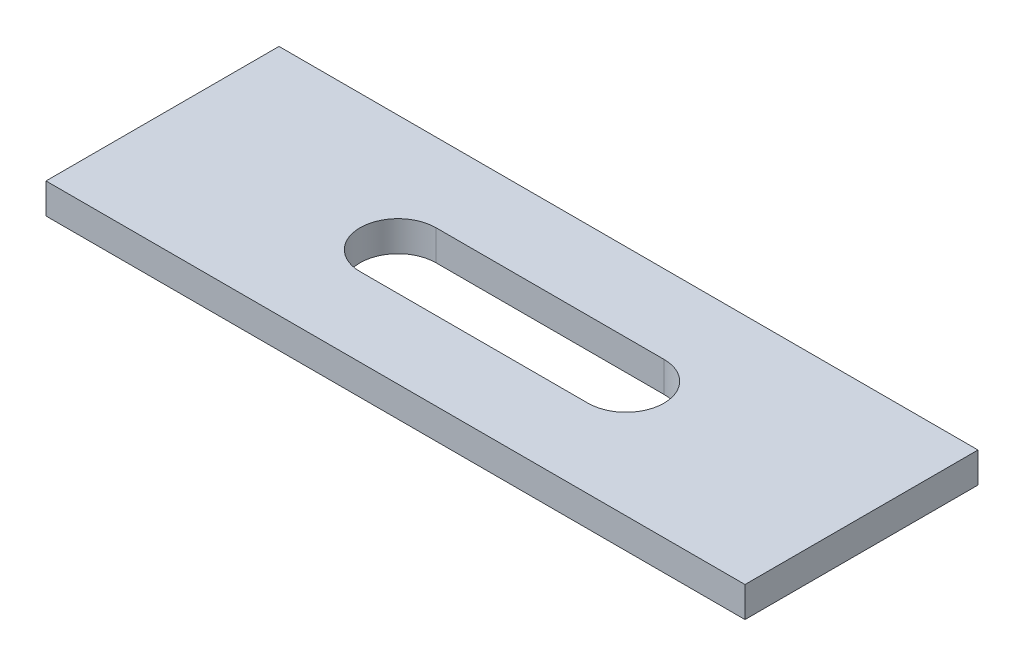
SolidWorks part; units mm, degrees
material "Pine"
ref_plane "Front Plane" through (0, 0, 0) normal (0, 0, 1) x (1, 0, 0)
ref_plane "Top Plane" through (0, 0, 0) normal (0, 1, 0) x (1, 0, 0)
ref_plane "Right Plane" through (0, 0, 0) normal (1, 0, 0) x (0, 0, -1)
sketch "Sketch2" plane through (0, 0, 0) normal (0, 1, 0) x (1, 0, 0)
  line L4 (93, 46) -> (183, 46) construction
  line L5 (0, 0) -> (276, 0)
  line L6 (0, 0) -> (0, 92)
  line L7 (0, 92) -> (276, 92)
  line L8 (276, 0) -> (276, 92)
  line L9 (93, 61) -> (183, 61)
  line L10 (93, 31) -> (183, 31)
  arc A0 (93, 61) -> (93, 31) centre (93, 46) ccw
  arc A1 (183, 31) -> (183, 61) centre (183, 46) ccw
  point P7 (138, 46)
  dimension "D3" = 46
  dimension "D5" = 15
  dimension "D1" = 92
  dimension "D2" = 276
  dimension "D4" = 93
  dimension "D6" = 90
extrude "Boss-Extrude1" add sketch "Sketch2" along normal blind 12 contours L7 L8 L5 L6
extrude "Cut-Extrude1" cut sketch "Sketch2<3>" along normal up to surface (12 mm away) contours A0 L10 A1 L9 up to face at (138, 12, -46)
sketch "Sketch2<3>" plane through (0, 0, 0) normal (0, 1, 0) x (1, 0, 0) same geometry as "Sketch2"
equation "\"LENGTH\" = 900mm"
equation "\"PLY\"= 12mm"
equation "\"D1@Boss-Extrude1\"=\"PLY\""
